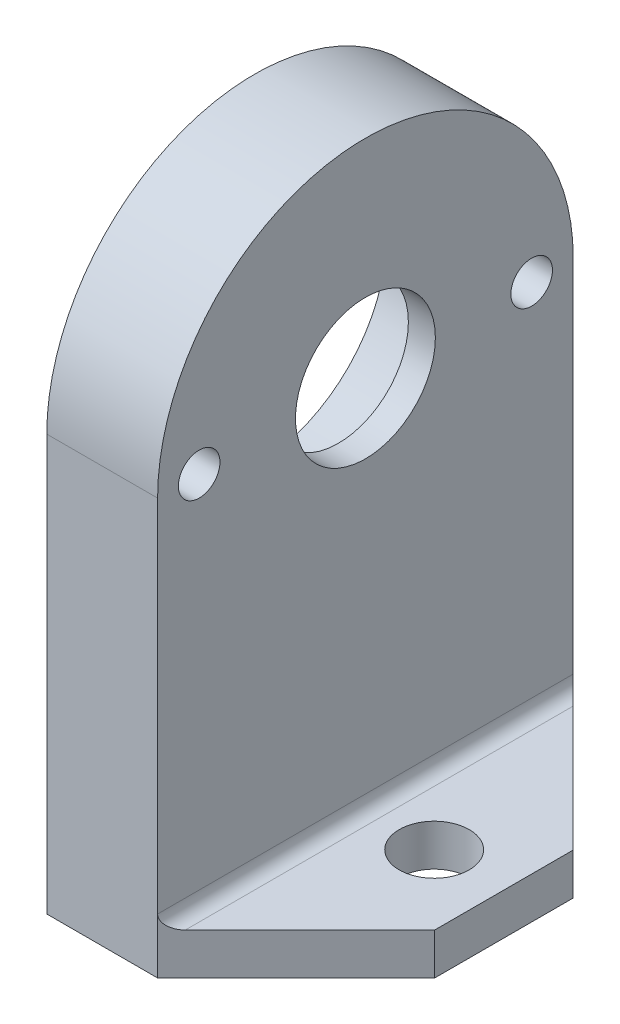
SolidWorks part; units mm, degrees
ref_plane "Front Plane" through (0, 0, 0) normal (0, 0, 1) x (1, 0, 0)
ref_plane "Top Plane" through (0, 0, 0) normal (0, 1, 0) x (1, 0, 0)
ref_plane "Right Plane" through (0, 0, 0) normal (1, 0, 0) x (0, 0, -1)
sketch "Sketch2" plane through (0, 0, 0) normal (1, 0, 0) x (0, 0, -1)
  line L0 (15, 0) -> (0, 0)
  line L1 (0, 0) -> (-15, 0)
  line L2 (-15, 0) -> (-15, 30)
  line L3 (15, 30) -> (15, 0)
  arc A0 (-15, 30) -> (15, 30) centre (0, 30) cw
  circle A1 centre (0, 30) radius 9.525
  circle A2 centre (0, 30) radius 5.05
  circle A3 centre (0, 10) radius 2.525
  circle A4 centre (12, 30) radius 1.5
  circle A5 centre (-12, 30) radius 1.5
  dimension "D3" = 19.05
  dimension "D4" = 10.1
  dimension "D6" = 5.05
  dimension "D8" = 3
  dimension "D9" = 3
  dimension "D2" = 30
  dimension "D1" = 30
  dimension "D5" = 10
  dimension "D7" = 15
  dimension "D10" = 3
  dimension "D11" = 3
extrude "Boss-Extrude1" add sketch "Sketch2" along normal mid plane 8 contours A0 L2 L1 L0 L3 A3 A1 | A3 region at (0, 18.3869, 0) region at (0, 10, 0)
extrude "Boss-Extrude2" add sketch "Sketch2<4>" against normal blind 1.95 from surface contours A1 A2 region at (0, 30, 9.2556) starting at face at (4, 30, 10.5)
sketch "Sketch2<4>" plane through (0, 0, 0) normal (1, 0, 0) x (0, 0, -1) same geometry as "Sketch2"
sketch "Sketch3" plane through (0, 0, 0) normal (0, -1, 0) x (1, 0, 0)
  line L9 (4, 15) -> (14, 15)
  line L10 (4, 15) -> (4, -15)
  line L11 (4, -15) -> (14, -15)
  line L12 (14, 15) -> (14, -15)
  point P0 (0, 0)
  dimension "D1" = 30
  dimension "D2" = 10
extrude "Boss-Extrude3" add sketch "Sketch3" against normal blind 3
sketch "Sketch4" plane through (0, 0, 0) normal (0, -1, 0) x (-1, 0, 0)
  line L0 (-14, 15) -> (-3.9284, -15) construction
  line L2 (-14, 15) -> (4, 15) construction
  line L3 (-14, -15) -> (-14, 15) construction
  line L4 (-14, -15) -> (4, -15) construction
  circle A0 centre (-8.9642, 0) radius 2.525
  dimension "D5" = 5.05
extrude "Cut-Extrude1" cut sketch "Sketch4" against normal through all contours A0
chamfer "Chamfer1" distance 10 angle 45 2 edges at (14, 1.5, -15) (14, 1.5, 15)
fillet "Fillet2" radius 1 1 edges at (4, 3, 0)
equation "\"D7@Sketch2\"=\"D1@Sketch2\"/2"
equation "\"D1@Sketch3\"=\"D1@Sketch2\""
